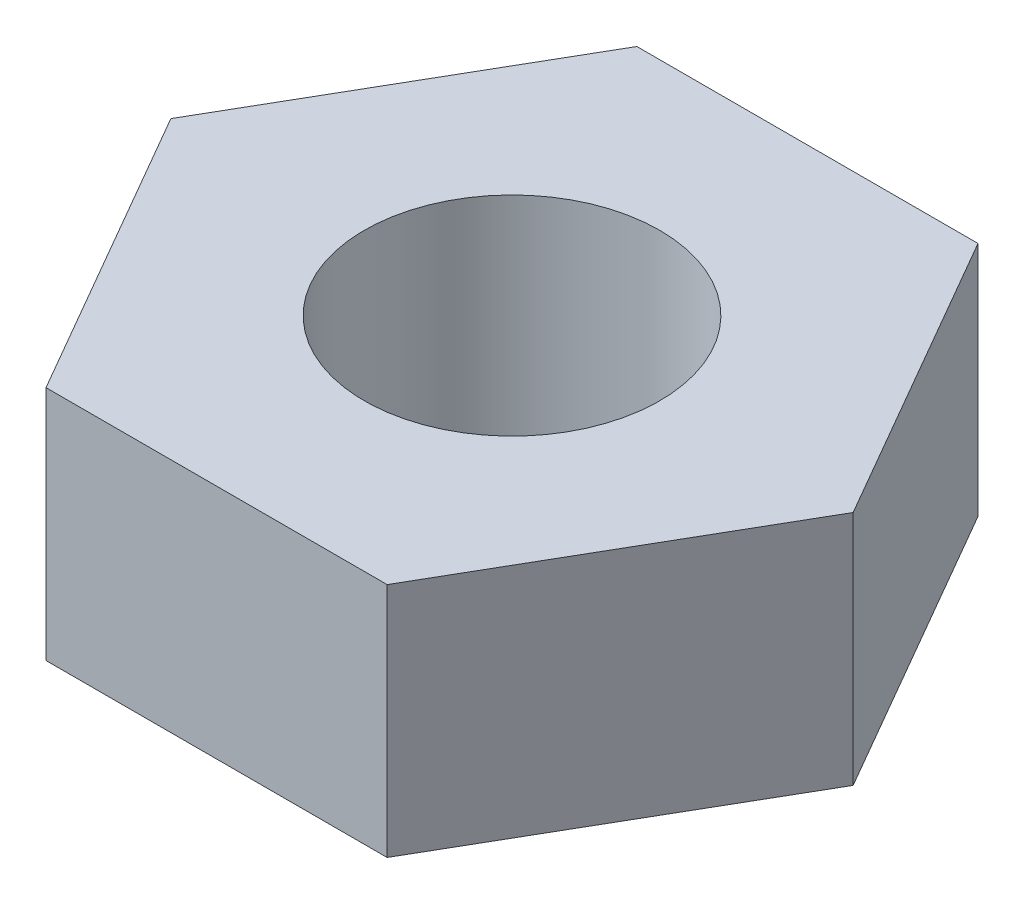
SolidWorks part; units mm, degrees
ref_plane "前视基准面" through (0, 0, 0) normal (0, 0, 1) x (1, 0, 0)
ref_plane "上视基准面" through (0, 0, 0) normal (0, 1, 0) x (1, 0, 0)
ref_plane "右视基准面" through (0, 0, 0) normal (1, 0, 0) x (0, 0, -1)
other "Configuration Table"
sketch "草图1" plane through (0, 0, 0) normal (0, 1, 0) x (1, 0, 0)
  line L1 (2.3094, 0) -> (1.1547, 2)
  line L2 (1.1547, 2) -> (-1.1547, 2)
  line L3 (-1.1547, 2) -> (-2.3094, 0)
  line L4 (-2.3094, 0) -> (-1.1547, -2)
  line L5 (-1.1547, -2) -> (1.1547, -2)
  line L6 (1.1547, -2) -> (2.3094, 0)
  circle A0 centre (0, 0) radius 2 construction
  dimension "D1" = 4
extrude "凸台-拉伸1" add sketch "草图1" along normal blind 1.6
sketch "草图3" plane through (0, 0, 0) normal (0, -1, 0) x (1, 0, 0)
  circle A0 centre (0, 0) radius 1
  dimension "D1" = 2
extrude "切除-拉伸1" cut sketch "草图3" against normal through all
ref_axis "基准轴1" through (0, 4.8881, 0) along (0, -1, 0)
